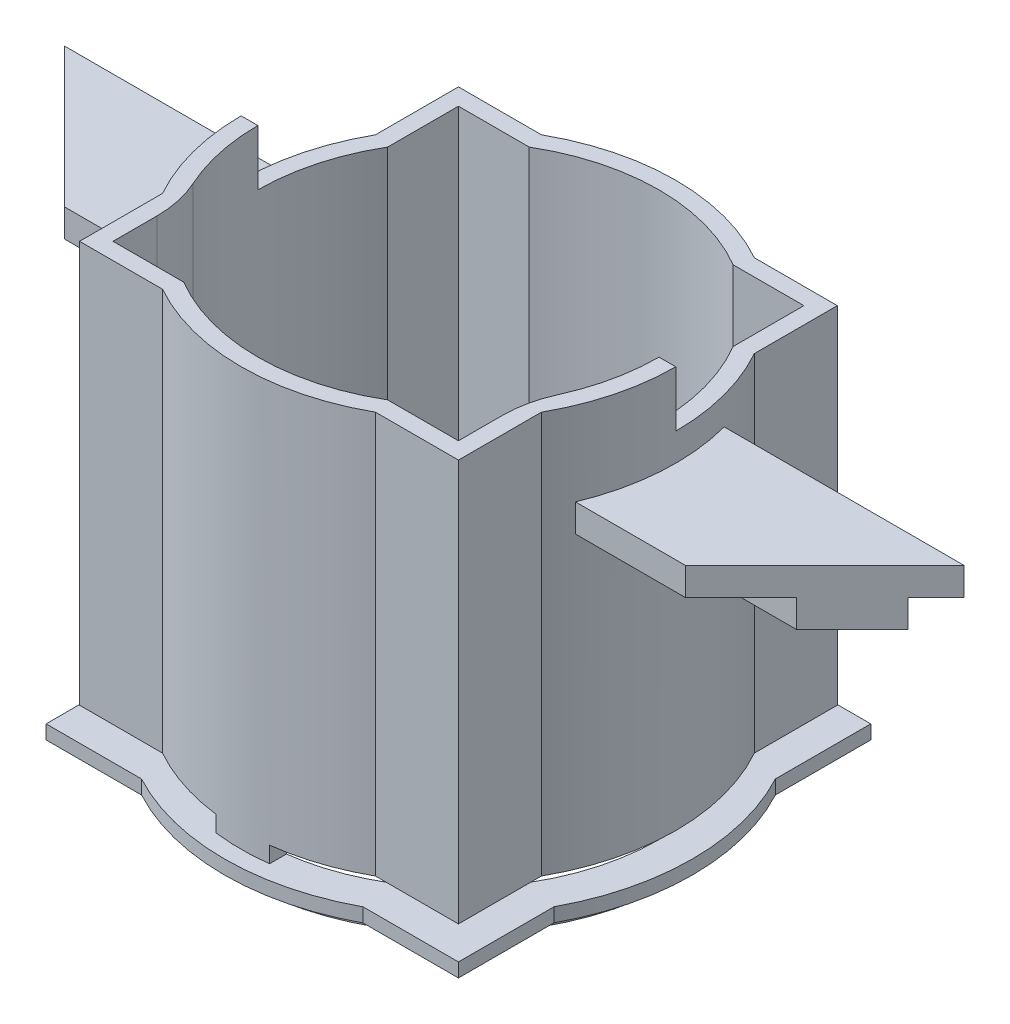
SolidWorks part; units mm, degrees
ref_plane "Front Plane" through (0, 0, 0) normal (0, 0, 1) x (1, 0, 0)
ref_plane "Top Plane" through (0, 0, 0) normal (0, 1, 0) x (1, 0, 0)
ref_plane "Right Plane" through (0, 0, 0) normal (1, 0, 0) x (0, 0, -1)
sketch "Sketch1" plane through (0, 0, 0) normal (0, 1, 0) x (1, 0, 0)
  line L0 (23.2448, 39.37) -> (39.37, 39.37)
  line L1 (-39.37, -39.37) -> (-23.2448, -39.37)
  line L2 (-39.37, -39.37) -> (-39.37, -23.2448)
  line L3 (-39.37, 39.37) -> (-23.2448, 39.37)
  line L4 (39.37, -39.37) -> (39.37, -23.2448)
  line L5 (-39.37, -39.37) -> (39.37, 39.37) construction
  line L6 (-39.37, 39.37) -> (39.37, -39.37) construction
  line L7 (39.37, 23.2448) -> (39.37, 39.37)
  line L8 (-39.37, 23.2448) -> (-39.37, 39.37)
  line L9 (23.2448, -39.37) -> (39.37, -39.37)
  line L10 (24.2633, 43.18) -> (43.18, 43.18)
  line L11 (43.18, 24.2633) -> (43.18, 43.18)
  line L12 (43.18, -43.18) -> (43.18, -24.2633)
  line L13 (24.2633, -43.18) -> (43.18, -43.18)
  line L14 (-43.18, -43.18) -> (-24.2633, -43.18)
  line L15 (-43.18, -43.18) -> (-43.18, -24.2633)
  line L16 (-43.18, 24.2633) -> (-43.18, 43.18)
  line L17 (-43.18, 43.18) -> (-24.2633, 43.18)
  arc A1 (-39.37, 23.2448) -> (-39.37, -23.2448) centre (0, 0) ccw
  arc A2 (23.2448, 39.37) -> (-23.2448, 39.37) centre (0, 0) ccw
  arc A3 (-23.2448, -39.37) -> (23.2448, -39.37) centre (0, 0) ccw
  arc A4 (39.37, -23.2448) -> (39.37, 23.2448) centre (0, 0) ccw
  arc A5 (43.18, -24.2633) -> (43.18, 24.2633) centre (0, 0) ccw
  arc A6 (-24.2633, -43.18) -> (24.2633, -43.18) centre (0, 0) ccw
  arc A7 (-43.18, 24.2633) -> (-43.18, -24.2633) centre (0, 0) ccw
  arc A8 (24.2633, 43.18) -> (-24.2633, 43.18) centre (0, 0) ccw
  point P0 (0, 0)
  dimension "D1" = 78.74
  dimension "D2" = 78.74
  dimension "D3" = 91.44
  dimension "D4" = 3.81
extrude "Boss-Extrude1" add sketch "Sketch1" along normal blind 101.6
sketch "Sketch6" plane through (0, 0, 0) normal (0, 0, 1) x (1, 0, 0)
  line L1 (-56.642, 10.033) -> (-6.096, 10.033)
  line L2 (-56.642, 10.033) -> (-56.642, 6.35)
  line L3 (-56.642, 6.35) -> (-6.096, 6.35)
  line L5 (-43.18, 0) -> (-24.2633, 0) construction
  line L8 (-6.096, 10.033) -> (-6.096, 6.35)
  line L9 (0, 0) -> (0, 21.9448) construction
  line L10 (6.096, 10.033) -> (6.096, 6.35)
  line L11 (56.642, 6.35) -> (6.096, 6.35)
  line L12 (56.642, 10.033) -> (6.096, 10.033)
  line L13 (56.642, 10.033) -> (56.642, 6.35)
  dimension "D3" = 3.683
  dimension "D1" = 6.096
  dimension "D4" = 6.35
extrude "Cut-Extrude4" cut sketch "Sketch6" against normal through all both and the other way through all
ref_plane "Plane1" through (0, 69.85, 0) normal (0, 1, 0) x (1, 0, 0)
sketch "Sketch9" plane through (0, 69.85, 0) normal (0, 1, 0) x (1, 0, 0)
  line L1 (-83.4526, -6.35) -> (-49.1213, -6.35)
  line L3 (-96.1526, 6.35) -> (-49.1213, 6.35)
  line L7 (-96.1526, 6.35) -> (-83.4526, -6.35)
  arc A0 (-43.18, 24.2633) -> (-43.18, -24.2633) centre (0, 0) ccw construction
  arc A1 (-49.1213, 6.35) -> (-49.1213, -6.35) centre (0, 0) ccw
  point P0 (0, 0)
  point P1 (0, 0)
  point P2 (-89.8026, 0)
  dimension "D1" = 96.1526
  dimension "D2" = 45
  dimension "D4" = 12.7
extrude "Boss-Extrude6" add sketch "Sketch9" along normal blind 12.7
sketch "Sketch11" plane through (0, 82.55, 0) normal (0, 1, 0) x (1, 0, 0)
  line L0 (-70.7526, -19.05) -> (-70.7526, 12.7) construction
  line L1 (-70.7526, 12.7) -> (-102.5026, 12.7)
  line L2 (-102.5026, 12.7) -> (-70.7526, -19.05)
  line L3 (-96.1526, 6.35) -> (-83.4526, -6.35) construction
  line L4 (-49.1213, 6.35) -> (-96.1526, 6.35) construction
  line L5 (-83.4526, -6.35) -> (-49.1213, -6.35) construction
  line L6 (-70.7526, -19.05) -> (-45.72, -19.05)
  line L8 (-47.8741, 12.7) -> (-70.7526, 12.7)
  arc A0 (-43.18, 24.2633) -> (-43.18, -24.2633) centre (0, 0) ccw construction
  arc A2 (-47.8741, 12.7) -> (-45.72, -19.05) centre (0, 0) ccw
  point P2 (0, 0)
  point P11 (0, 0)
  dimension "D1" = 6.35
  dimension "D2" = 12.7
extrude "Boss-Extrude8" add sketch "Sketch11" against normal blind 6.35
mirror "Mirror1" about plane through (0, 0, 0) normal (1, 0, 0) of "Boss-Extrude6", "Boss-Extrude8"
sketch "Sketch12" plane through (0, 101.6, 0) normal (0, -1, 0) x (1, 0, 0)
  line L0 (25.2408, -46.99) -> (46.99, -46.99)
  line L1 (46.99, -46.99) -> (46.99, -25.2408)
  line L2 (46.99, 25.2408) -> (46.99, 46.99)
  line L3 (46.99, 46.99) -> (25.2408, 46.99)
  line L4 (-25.2408, 46.99) -> (-46.99, 46.99)
  line L5 (-46.99, 46.99) -> (-46.99, 25.2408)
  line L6 (-46.99, -25.2408) -> (-46.99, -46.99)
  line L7 (-46.99, -46.99) -> (-25.2408, -46.99)
  line L8 (24.2633, -43.18) -> (43.18, -43.18)
  line L9 (43.18, -43.18) -> (43.18, -24.2633)
  line L10 (43.18, 24.2633) -> (43.18, 43.18)
  line L11 (43.18, 43.18) -> (24.2633, 43.18)
  line L12 (-24.2633, 43.18) -> (-43.18, 43.18)
  line L13 (-43.18, 43.18) -> (-43.18, 24.2633)
  line L14 (-43.18, -24.2633) -> (-43.18, -43.18)
  line L15 (-43.18, -43.18) -> (-24.2633, -43.18)
  line L16 (24.2633, -43.18) -> (43.18, -43.18)
  line L17 (43.18, -43.18) -> (43.18, -24.2633)
  line L18 (43.18, 24.2633) -> (43.18, 43.18)
  line L19 (43.18, 43.18) -> (24.2633, 43.18)
  line L20 (-24.2633, 43.18) -> (-43.18, 43.18)
  line L21 (-43.18, 43.18) -> (-43.18, 24.2633)
  line L22 (-43.18, -24.2633) -> (-43.18, -43.18)
  line L23 (-43.18, -43.18) -> (-24.2633, -43.18)
  arc A0 (46.99, -25.2408) -> (46.99, 25.2408) centre (0, 0) ccw
  arc A3 (25.2408, 46.99) -> (-25.2408, 46.99) centre (0, 0) ccw
  arc A4 (-46.99, 25.2408) -> (-46.99, -25.2408) centre (0, 0) ccw
  arc A5 (-25.2408, -46.99) -> (25.2408, -46.99) centre (0, 0) ccw
  arc A7 (-24.2633, -43.18) -> (24.2633, -43.18) centre (0, 0) ccw
  arc A8 (43.18, -24.2633) -> (43.18, 24.2633) centre (0, 0) ccw
  arc A9 (24.2633, 43.18) -> (-24.2633, 43.18) centre (0, 0) ccw
  arc A10 (-43.18, 24.2633) -> (-43.18, -24.2633) centre (0, 0) ccw
  arc A11 (-24.2633, -43.18) -> (24.2633, -43.18) centre (0, 0) ccw
  arc A12 (43.18, -24.2633) -> (43.18, 24.2633) centre (0, 0) ccw
  arc A13 (24.2633, 43.18) -> (-24.2633, 43.18) centre (0, 0) ccw
  arc A14 (-43.18, 24.2633) -> (-43.18, -24.2633) centre (0, 0) ccw
  dimension "D1" = 0
  dimension "D2" = 3.81
extrude "Boss-Extrude9" add sketch "Sketch12" along normal blind 3.175 from surface starting at face at (-28.9674, 6.35, 0)
sketch "Sketch13" plane through (0, 0, 0) normal (0, 0, 1) x (1, 0, 0)
  line L0 (24.2633, 101.6) -> (-24.2633, 101.6) construction
  line L1 (-71.4448, 101.6) -> (67.7277, 101.6)
  line L2 (-71.4448, 101.6) -> (-71.4448, 88.9)
  line L3 (-71.4448, 88.9) -> (67.7277, 88.9)
  line L4 (67.7277, 101.6) -> (67.7277, 88.9)
  point P6 (67.7277, 101.6)
  dimension "D1" = 12.7
extrude "Cut-Extrude6" cut sketch "Sketch13" against normal through all
fillet "Fillet1" radius 25.4 2 edges at (39.37, 55.8165, 23.2448) (-39.37, 55.8165, 23.2448)
sketch "Sketch16" plane through (0, 6.35, 0) normal (0, 1, 0) x (1, 0, 0)
  line L1 (-19.05, 58.42) -> (19.05, 58.42)
  line L2 (-19.05, 58.42) -> (-19.05, 45.72)
  line L3 (-19.05, 45.72) -> (19.05, 45.72)
  line L4 (19.05, 58.42) -> (19.05, 45.72)
  line L5 (-19.05, 58.42) -> (19.05, 45.72) construction
  line L6 (-19.05, 45.72) -> (19.05, 58.42) construction
  arc A0 (23.2448, 39.37) -> (-23.2448, 39.37) centre (0, 0) ccw construction
  point P0 (0, 52.07)
  point P8 (0, 0)
  dimension "D1" = 12.7
  dimension "D2" = 38.1
extrude "Boss-Extrude13" add sketch "Sketch16" against normal blind 3.175
sketch "Sketch18" plane through (0, 6.35, 0) normal (0, 1, 0) x (1, 0, 0)
  line L0 (-19.05, 58.42) -> (-19.05, 49.8222) construction
  line L1 (19.05, 58.42) -> (-19.05, 58.42) construction
  circle A0 centre (-12.7, 52.07) radius 3.175
  point P4 (0, 0)
  dimension "D2" = 6.35
  dimension "D1" = 6.35
  dimension "D3" = 6.35
extrude "Boss-Extrude14" add sketch "Sketch18" along normal blind 6.35
mirror "Mirror2" about plane through (0, 0, 0) normal (1, 0, 0) of "Boss-Extrude14"
equation "\"tightTol\" = 0.005in"
equation "\"normTol\"= 0.01in"
equation "\"looseTol\"= 0.02in"
equation "\"D1@Sketch6\" = 0.250000in - \"normTol\""
equation "\"D3@Sketch6\"=\"looseTol\"+0.125000in"
